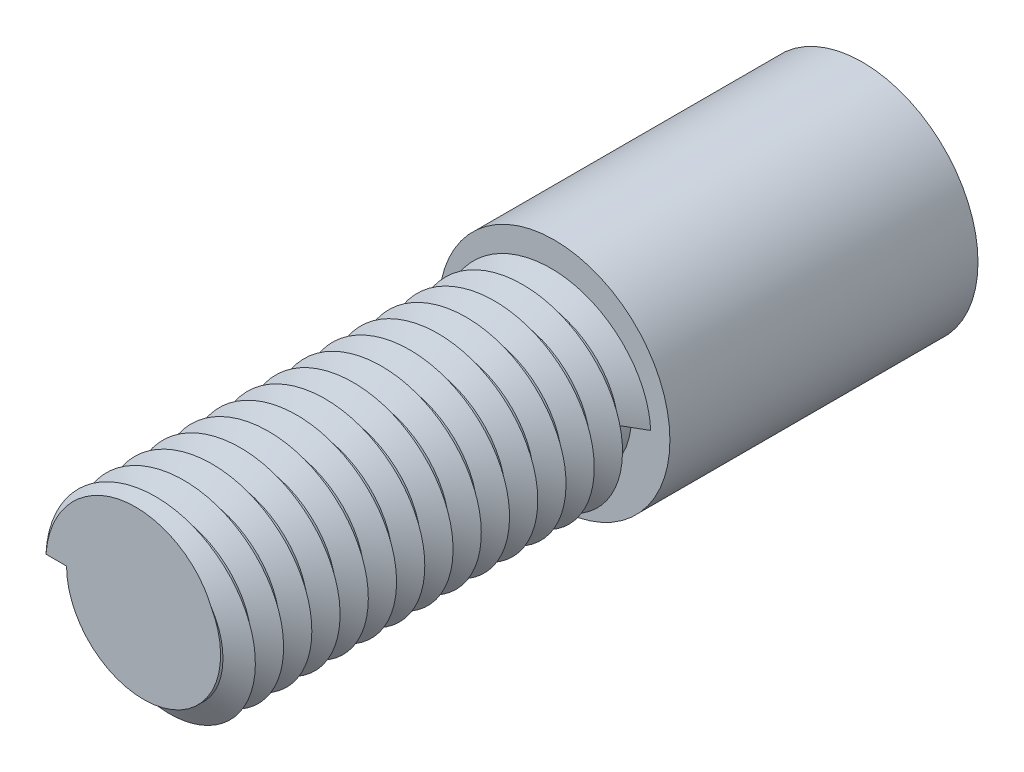
SolidWorks part; units mm, degrees
material "Aluminum"
ref_plane "Front Plane" through (0, 0, 0) normal (0, 0, 1) x (1, 0, 0)
ref_plane "Top Plane" through (0, 0, 0) normal (0, 1, 0) x (1, 0, 0)
ref_plane "Right Plane" through (0, 0, 0) normal (1, 0, 0) x (0, 0, -1)
sketch "Sketch1" plane through (0, 0, 0) normal (0, 0, 1) x (1, 0, 0)
  circle A0 centre (0, 0) radius 1.5
  dimension "D1" = 3
extrude "Boss-Extrude1" add sketch "Sketch1" along normal blind 8
sketch "Sketch2" plane through (0, 0, 0) normal (0, 0, -1) x (-1, 0, 0)
  circle A0 centre (0, 0) radius 2.25
  dimension "D1" = 4.5
extrude "Boss-Extrude2" add sketch "Sketch2" along normal blind 6
sketch "Sketch3" plane through (0, 0, -6) normal (0, 0, -1) x (-1, 0, 0)
  circle A0 centre (0, 0) radius 1.5
  dimension "D1" = 3
extrude "Cut-Extrude1" cut sketch "Sketch3" against normal blind 4.5
ref_plane "Plane1" through (0, 0, 8) normal (0, 0, 1) x (1, 0, 0)
sketch "Sketch4" plane through (0, 0, 8) normal (0, 0, 1) x (1, 0, 0)
  circle A0 centre (0, 0) radius 1.5
curve "Helix/Spiral1" pitch 0.55 height 7.975 radius 1.5 centre (0, 0, 8) axis (0, 0, -1) start towards (1, 0, 0)
sketch "Sketch5" plane through (0, 0, 0) normal (0, 1, 0) x (1, 0, 0)
  line L0 (-2.8615, -8) -> (2.8615, -8) construction
  line L1 (-1.9, -8) -> (-1.3, -8.3464)
  line L2 (-1.3, -8.3464) -> (-1.3, -7.6536)
  line L3 (-1.3, -7.6536) -> (-1.9, -8)
  circle A0 centre (-1.5, -8) radius 0.2 construction
  spline S0 degree 3 poles (-1.5, -8) (-1.5, -7.9886) (-1.4219, -7.9656) (-1.0883, -7.9313) (-0.589, -7.8969) (0, -7.8625) (0.589, -7.8281) (1.0883, -7.7938) (1.4219, -7.7594) (1.5391, -7.725) (1.4219, -7.6906) (1.0883, -7.6563) (0.589, -7.6219) (0, -7.5875) (-0.589, -7.5531) (-1.0883, -7.5188) (-1.4219, -7.4844) (-1.5391, -7.45) (-1.4219, -7.4156) (-1.0883, -7.3813) (-0.589, -7.3469) (0, -7.3125) (0.589, -7.2781) (1.0883, -7.2437) (1.4219, -7.2094) (1.5391, -7.175) (1.4219, -7.1406) (1.0883, -7.1062) (0.589, -7.0719) (0, -7.0375) (-0.589, -7.0031) (-1.0883, -6.9687) (-1.4219, -6.9344) (-1.5391, -6.9) (-1.4219, -6.8656) (-1.0883, -6.8313) (-0.589, -6.7969) (0, -6.7625) (0.589, -6.7281) (1.0883, -6.6938) (1.4219, -6.6594) (1.5391, -6.625) (1.4219, -6.5906) (1.0883, -6.5563) (0.589, -6.5219) (0, -6.4875) (-0.589, -6.4531) (-1.0883, -6.4188) (-1.4219, -6.3844) (-1.5391, -6.35) (-1.4219, -6.3156) (-1.0883, -6.2813) (-0.589, -6.2469) (0, -6.2125) (0.589, -6.1781) (1.0883, -6.1438) (1.4219, -6.1094) (1.5391, -6.075) (1.4219, -6.0406) (1.0883, -6.0063) (0.589, -5.9719) (0, -5.9375) (-0.589, -5.9031) (-1.0883, -5.8688) (-1.4219, -5.8344) (-1.5391, -5.8) (-1.4219, -5.7656) (-1.0883, -5.7313) (-0.589, -5.6969) (0, -5.6625) (0.589, -5.6281) (1.0883, -5.5938) (1.4219, -5.5594) (1.5391, -5.525) (1.4219, -5.4906) (1.0883, -5.4563) (0.589, -5.4219) (0, -5.3875) (-0.589, -5.3531) (-1.0883, -5.3188) (-1.4219, -5.2844) (-1.5391, -5.25) (-1.4219, -5.2156) (-1.0883, -5.1813) (-0.589, -5.1469) (0, -5.1125) (0.589, -5.0781) (1.0883, -5.0437) (1.4219, -5.0094) (1.5391, -4.975) (1.4219, -4.9406) (1.0883, -4.9063) (0.589, -4.8719) (0, -4.8375) (-0.589, -4.8031) (-1.0883, -4.7687) (-1.4219, -4.7344) (-1.5391, -4.7) (-1.4219, -4.6656) (-1.0883, -4.6312) (-0.589, -4.5969) (0, -4.5625) (0.589, -4.5281) (1.0883, -4.4937) (1.4219, -4.4594) (1.5391, -4.425) (1.4219, -4.3906) (1.0883, -4.3562) (0.589, -4.3219) (0, -4.2875) (-0.589, -4.2531) (-1.0883, -4.2187) (-1.4219, -4.1844) (-1.5391, -4.15) (-1.4219, -4.1156) (-1.0883, -4.0812) (-0.589, -4.0469) (0, -4.0125) (0.589, -3.9781) (1.0883, -3.9437) (1.4219, -3.9094) (1.5391, -3.875) (1.4219, -3.8406) (1.0883, -3.8063) (0.589, -3.7719) (0, -3.7375) (-0.589, -3.7031) (-1.0883, -3.6688) (-1.4219, -3.6344) (-1.5391, -3.6) (-1.4219, -3.5656) (-1.0883, -3.5313) (-0.589, -3.4969) (0, -3.4625) (0.589, -3.4281) (1.0883, -3.3938) (1.4219, -3.3594) (1.5391, -3.325) (1.4219, -3.2906) (1.0883, -3.2563) (0.589, -3.2219) (0, -3.1875) (-0.589, -3.1531) (-1.0883, -3.1188) (-1.4219, -3.0844) (-1.5391, -3.05) (-1.4219, -3.0156) (-1.0883, -2.9813) (-0.589, -2.9469) (0, -2.9125) (0.589, -2.8781) (1.0883, -2.8438) (1.4219, -2.8094) (1.5391, -2.775) (1.4219, -2.7406) (1.0883, -2.7063) (0.589, -2.6719) (0, -2.6375) (-0.589, -2.6031) (-1.0883, -2.5688) (-1.4219, -2.5344) (-1.5391, -2.5) (-1.4219, -2.4656) (-1.0883, -2.4313) (-0.589, -2.3969) (0, -2.3625) (0.589, -2.3281) (1.0883, -2.2938) (1.4219, -2.2594) (1.5391, -2.225) (1.4219, -2.1906) (1.0883, -2.1563) (0.589, -2.1219) (0, -2.0875) (-0.589, -2.0531) (-1.0883, -2.0188) (-1.4219, -1.9844) (-1.5391, -1.95) (-1.4219, -1.9156) (-1.0883, -1.8813) (-0.589, -1.8469) (0, -1.8125) (0.589, -1.7781) (1.0883, -1.7438) (1.4219, -1.7094) (1.5391, -1.675) (1.4219, -1.6406) (1.0883, -1.6063) (0.589, -1.5719) (0, -1.5375) (-0.589, -1.5031) (-1.0883, -1.4688) (-1.4219, -1.4344) (-1.5391, -1.4) (-1.4219, -1.3656) (-1.0883, -1.3313) (-0.589, -1.2969) (0, -1.2625) (0.589, -1.2281) (1.0883, -1.1938) (1.4219, -1.1594) (1.5391, -1.125) (1.4219, -1.0906) (1.0883, -1.0563) (0.589, -1.0219) (0, -0.9875) (-0.589, -0.9531) (-1.0883, -0.9188) (-1.4219, -0.8844) (-1.5391, -0.85) (-1.4219, -0.8156) (-1.0883, -0.7813) (-0.589, -0.7469) (0, -0.7125) (0.589, -0.6781) (1.0883, -0.6438) (1.4219, -0.6094) (1.5391, -0.575) (1.4219, -0.5406) (1.0883, -0.5062) (0.589, -0.4719) (0, -0.4375) (-0.589, -0.4031) (-1.0883, -0.3687) (-1.4219, -0.3344) (-1.5391, -0.3) (-1.4219, -0.2656) (-1.0883, -0.2312) (-0.589, -0.1969) (0, -0.1625) (0.589, -0.1281) (1.0883, -0.0937) (1.4219, -0.0594) (1.5, -0.0364) (1.5, -0.025) knots 0 0 0 0 0.00431 0.008621 0.012931 0.017241 0.021552 0.025862 0.030172 0.034483 0.038793 0.043103 0.047414 0.051724 0.056034 0.060345 0.064655 0.068966 0.073276 0.077586 0.081897 0.086207 0.090517 0.094828 0.099138 0.103448 0.107759 0.112069 0.116379 0.12069 0.125 0.12931 0.133621 0.137931 0.142241 0.146552 0.150862 0.155172 0.159483 0.163793 0.168103 0.172414 0.176724 0.181034 0.185345 0.189655 0.193966 0.198276 0.202586 0.206897 0.211207 0.215517 0.219828 0.224138 0.228448 0.232759 0.237069 0.241379 0.24569 0.25 0.25431 0.258621 0.262931 0.267241 0.271552 0.275862 0.280172 0.284483 0.288793 0.293103 0.297414 0.301724 0.306034 0.310345 0.314655 0.318966 0.323276 0.327586 0.331897 0.336207 0.340517 0.344828 0.349138 0.353448 0.357759 0.362069 0.366379 0.37069 0.375 0.37931 0.383621 0.387931 0.392241 0.396552 0.400862 0.405172 0.409483 0.413793 0.418103 0.422414 0.426724 0.431034 0.435345 0.439655 0.443966 0.448276 0.452586 0.456897 0.461207 0.465517 0.469828 0.474138 0.478448 0.482759 0.487069 0.491379 0.49569 0.5 0.50431 0.508621 0.512931 0.517241 0.521552 0.525862 0.530172 0.534483 0.538793 0.543103 0.547414 0.551724 0.556034 0.560345 0.564655 0.568966 0.573276 0.577586 0.581897 0.586207 0.590517 0.594828 0.599138 0.603448 0.607759 0.612069 0.616379 0.62069 0.625 0.62931 0.633621 0.637931 0.642241 0.646552 0.650862 0.655172 0.659483 0.663793 0.668103 0.672414 0.676724 0.681034 0.685345 0.689655 0.693966 0.698276 0.702586 0.706897 0.711207 0.715517 0.719828 0.724138 0.728448 0.732759 0.737069 0.741379 0.74569 0.75 0.75431 0.758621 0.762931 0.767241 0.771552 0.775862 0.780172 0.784483 0.788793 0.793103 0.797414 0.801724 0.806034 0.810345 0.814655 0.818966 0.823276 0.827586 0.831897 0.836207 0.840517 0.844828 0.849138 0.853448 0.857759 0.862069 0.866379 0.87069 0.875 0.87931 0.883621 0.887931 0.892241 0.896552 0.900862 0.905172 0.909483 0.913793 0.918103 0.922414 0.926724 0.931034 0.935345 0.939655 0.943966 0.948276 0.952586 0.956897 0.961207 0.965517 0.969828 0.974138 0.978448 0.982759 0.987069 0.991379 0.99569 1 1 1 1 construction
  dimension "D1" = 0.4
sweep "Sweep1" add profiles "Sketch5" path "Helix/Spiral1"
sketch "Sketch6" plane through (0, 0, 8) normal (0, 0, 1) x (1, 0, 0)
  circle A0 centre (0, 0) radius 2.6014
extrude "Cut-Extrude2" cut sketch "Sketch6" along normal blind 1
